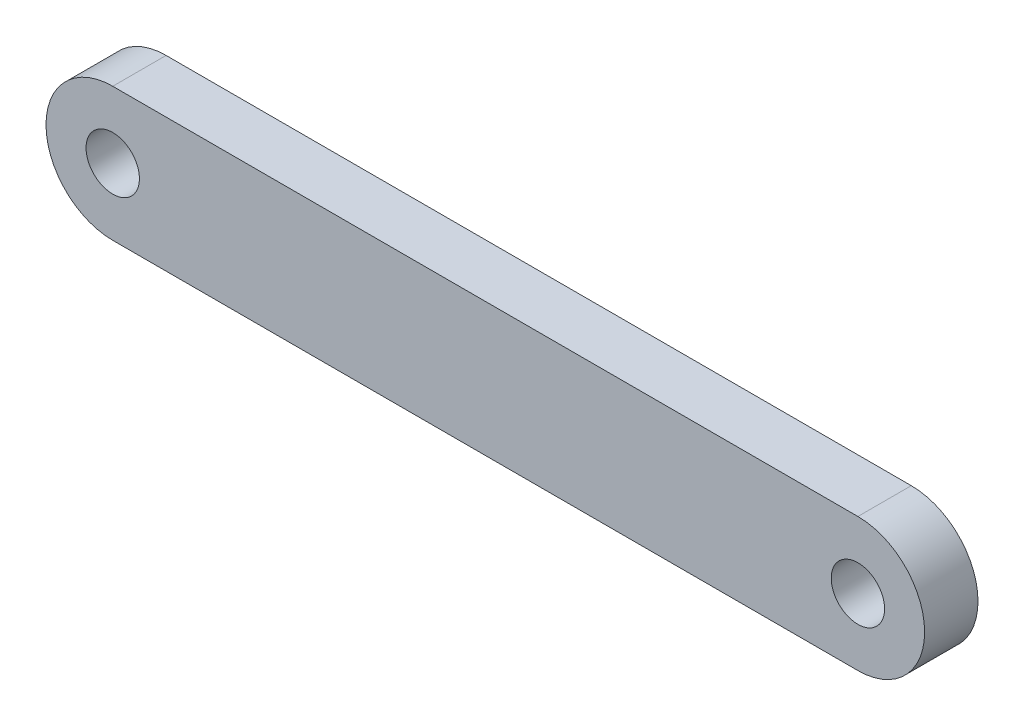
SolidWorks part; units mm, degrees
material "ABS"
ref_plane "Front Plane" through (0, 0, 0) normal (0, 0, 1) x (1, 0, 0)
ref_plane "Top Plane" through (0, 0, 0) normal (0, 1, 0) x (1, 0, 0)
ref_plane "Right Plane" through (0, 0, 0) normal (1, 0, 0) x (0, 0, -1)
sketch "Sketch1" plane through (0, 0, 0) normal (0, 0, 1) x (1, 0, 0)
  line L0 (0, 3.175) -> (35.4584, 3.175)
  line L1 (0, -3.175) -> (35.4584, -3.175)
  circle A0 centre (0, 0) radius 1.27
  circle A1 centre (0, 0) radius 3.175
  circle A2 centre (35.4584, 0) radius 1.27
  circle A3 centre (35.4584, 0) radius 3.175
  dimension "D1" = 2.54
  dimension "D2" = 6.35
  dimension "D3" = 35.4584
extrude "Boss-Extrude2" add sketch "Sketch1" along normal blind 2.54 contours A1 A0 | A3 A2 | A3 L0 A1 L1 region at (17.7292, 0, 0) region at (2.1816, 2.1816, 0) region at (37.64, 2.1816, 0)
